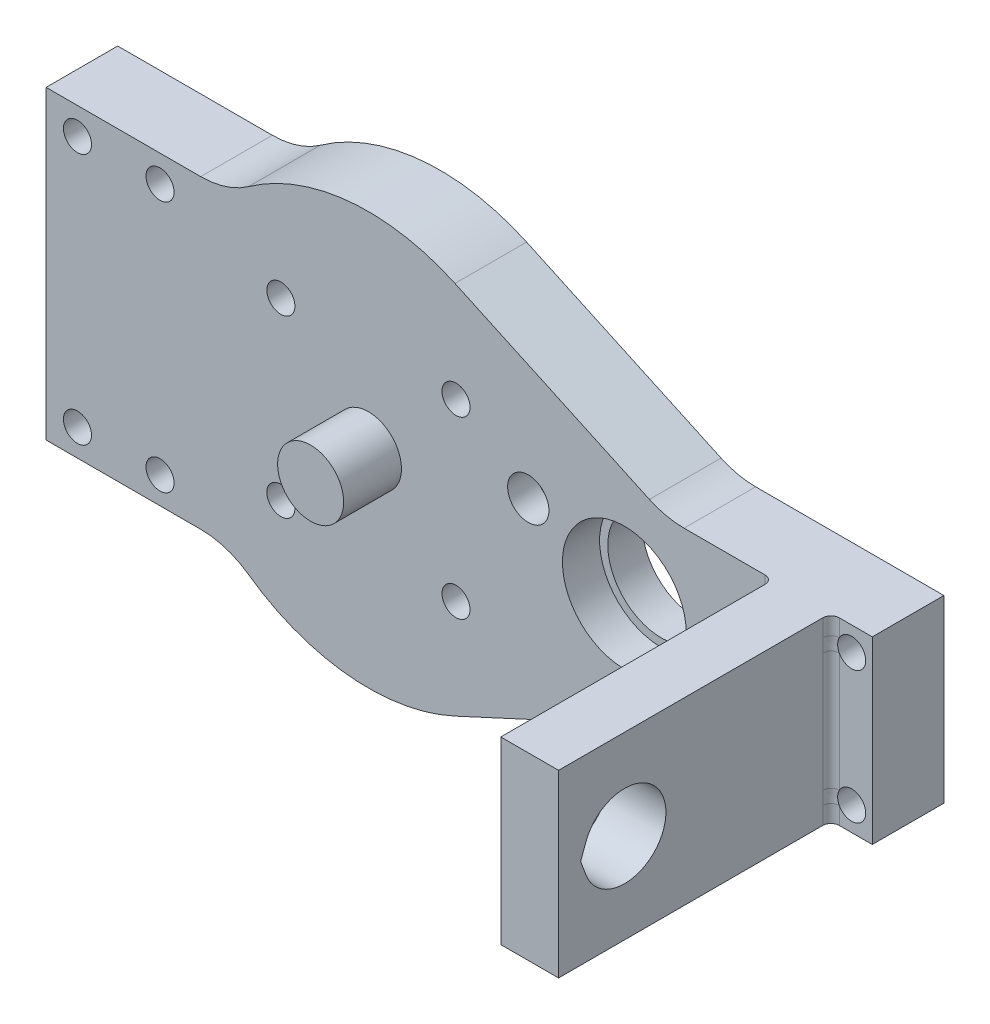
SolidWorks part; units mm, degrees
ref_plane "Front Plane" through (0, 0, 0) normal (0, 0, 1) x (1, 0, 0)
ref_plane "Top Plane" through (0, 0, 0) normal (0, 1, 0) x (1, 0, 0)
ref_plane "Right Plane" through (0, 0, 0) normal (1, 0, 0) x (0, 0, -1)
sketch "Sketch1" plane through (0, 0, 0) normal (0, 0, 1) x (1, 0, 0)
  line L0 (10.4839, 22.6956) -> (36.0323, 10.8939)
  line L1 (36.0323, -10.8939) -> (10.4839, -22.6956)
  circle A0 centre (0, 0) radius 22.215 construction
  circle A1 centre (31, 0) radius 10.2 construction
  arc A2 (10.4839, 22.6956) -> (10.4839, -22.6956) centre (0, 0) ccw
  arc A3 (36.0323, -10.8939) -> (36.0323, 10.8939) centre (31, 0) ccw
  dimension "D1" = 20.4
  dimension "D2" = 44.43
  dimension "D4" = 25
  dimension "D5" = 12
  dimension "D3" = 31
extrude "Boss-Extrude1" add sketch "Sketch1" along normal blind 4.5
sketch "Sketch2" plane through (0, 0, 4.5) normal (0, 0, 1) x (1, 0, 0)
  circle A0 centre (31, 0) radius 7.5
  dimension "D1" = 15
extrude "Cut-Extrude1" cut sketch "Sketch2" against normal through all
sketch "Sketch3" plane through (0, 0, 4.5) normal (0, 0, 1) x (1, 0, 0)
  circle A0 centre (0, 0) radius 4
  dimension "D1" = 8
extrude "Boss-Extrude2" add sketch "Sketch3" along normal blind 7
sketch "Sketch4" plane through (0, 0, 0) normal (0, 0, -1) x (-1, 0, 0)
  line L0 (-36.0323, 10.8939) -> (-56.0323, 10.8939)
  line L1 (-36.0323, -10.8939) -> (-56.0323, -10.8939)
  line L2 (-56.0323, -10.8939) -> (-56.0323, 10.8939)
  line L3 (22.5016, 10.8939) -> (42.5016, 10.8939)
  line L4 (42.5016, 10.8939) -> (42.5016, -10.8939)
  line L5 (42.5016, -10.8939) -> (22.5016, -10.8939)
  arc A0 (-10.4839, -22.6956) -> (-10.4839, 22.6956) centre (0, 0) ccw construction
  arc A1 (22.5016, -10.8939) -> (22.5016, 10.8939) centre (0, 0) ccw
  arc A2 (-36.0323, 10.8939) -> (-36.0323, -10.8939) centre (-31, 0) ccw construction
  arc A3 (-36.0323, 10.8939) -> (-36.0323, -10.8939) centre (-31, 0) ccw
  dimension "D1" = 20
  dimension "D2" = 20
extrude "Boss-Extrude3" add sketch "Sketch4" against normal up to surface (4.5 mm away) up to face at (4, 0, 4.5)
fillet "Fillet1" radius 10 4 edges at (-42.5016, 10.8939, 2.25) (-42.5016, -10.8939, 2.25) (56.0323, -10.8939, 2.25) (56.0323, 10.8939, 2.25)
sketch "Sketch8" plane through (0, 0, 4.5) normal (0, 0, 1) x (1, 0, 0)
  line L0 (56.0323, 0.8939) -> (56.0323, -0.8939) construction
  line L2 (56.0323, 0.8939) -> (56.0323, -0.8939)
  line L3 (55.4014, -4.3896) -> (55.4014, 4.3896)
  line L4 (-42.5016, -0.8939) -> (-42.5016, 0.8939) construction
  line L6 (-42.5016, -0.8939) -> (-42.5016, 0.8939)
  line L7 (-41.8707, 4.3896) -> (-41.8707, -4.3896)
  arc A0 (56.0323, 0.8939) -> (46.0323, 10.8939) centre (46.0323, 0.8939) ccw construction
  arc A1 (46.0323, -10.8939) -> (56.0323, -0.8939) centre (46.0323, -0.8939) ccw construction
  arc A2 (56.0323, 0.8939) -> (55.4014, 4.3896) centre (46.0323, 0.8939) ccw
  arc A3 (55.4014, -4.3896) -> (56.0323, -0.8939) centre (46.0323, -0.8939) ccw
  arc A4 (-32.5016, 10.8939) -> (-42.5016, 0.8939) centre (-32.5016, 0.8939) ccw construction
  arc A5 (-42.5016, -0.8939) -> (-32.5016, -10.8939) centre (-32.5016, -0.8939) ccw construction
  arc A6 (-41.8707, 4.3896) -> (-42.5016, 0.8939) centre (-32.5016, 0.8939) ccw
  arc A7 (-42.5016, -0.8939) -> (-41.8707, -4.3896) centre (-32.5016, -0.8939) ccw
extrude "Cut-Extrude4" cut sketch "Sketch8" against normal through all
sketch "Sketch9" plane through (0, 0, 4.5) normal (0, 0, 1) x (1, 0, 0)
  circle A0 centre (0, 0) radius 15 construction
  circle A1 centre (-10.6066, 10.6066) radius 1
  circle A2 centre (10.6066, 10.6066) radius 1
  circle A3 centre (10.6066, -10.6066) radius 1
  circle A4 centre (-10.6066, -10.6066) radius 1
  point P14 (0, 0)
  dimension "D1" = 30
  dimension "D2" = 2
  dimension "D3" = 4
extrude "Cut-Extrude5" cut sketch "Sketch9" against normal through all
sketch "Sketch10" plane through (0, 0, 4.5) normal (0, 0, 1) x (1, 0, 0)
  circle A0 centre (-10.6066, 10.6066) radius 1.7
  circle A1 centre (10.6066, 10.6066) radius 1.7
  circle A2 centre (10.6066, -10.6066) radius 1.7
  circle A3 centre (-10.6066, -10.6066) radius 1.7
  dimension "D1" = 3.4
extrude "Cut-Extrude6" cut sketch "Sketch10" against normal blind 2.4
sketch "Sketch11" plane through (0, 0, 0) normal (0, 0, -1) x (-1, 0, 0)
  line L0 (-40.9602, 14.6461) -> (-73.6718, 18.9155)
  line L1 (-73.6718, 18.9155) -> (-68.6403, -15.6759)
  line L2 (-68.6403, -15.6759) -> (-41.445, -13.2122)
  arc A0 (-40.9602, 14.6461) -> (-41.445, -13.2122) centre (0, 0) ccw
  dimension "D1" = 87
extrude "Cut-Extrude7" cut sketch "Sketch11" against normal up to surface (4.5 mm away) up to face at (-8.9066, -10.6066, 4.5)
fillet "Fillet2" radius 10 2 edges at (42.1138, -10.8939, 2.25) (42.1138, 10.8939, 2.25)
sketch "Sketch12" plane through (0, 0, 4.5) normal (0, 0, 1) x (1, 0, 0)
  line L0 (-22.5016, 10.8939) -> (-42.5927, 14.8195)
  line L1 (-42.5927, 14.8195) -> (-48.1481, -13.6126)
  line L2 (-48.1481, -13.6126) -> (-27.4273, -14.3153)
  line L3 (-27.4273, -14.3153) -> (-22.5016, -10.8939)
  arc A0 (-22.5016, 10.8939) -> (-22.5016, -10.8939) centre (0, 0) ccw
extrude "Cut-Extrude8" cut sketch "Sketch12" against normal through all
sketch "Sketch23" plane through (0, 0, 0) normal (0, 0, -1) x (-1, 0, 0)
  line L2 (-36.0323, -10.8939) -> (-10.4839, -22.6956)
  line L3 (-10.4839, 22.6956) -> (-36.0323, 10.8939)
  line L4 (-36.0323, -10.8939) -> (-10.4839, -22.6956)
  line L5 (-10.4839, 22.6956) -> (-36.0323, 10.8939)
  circle A0 centre (-10.6066, -10.6066) radius 1 construction
  circle A1 centre (10.6066, -10.6066) radius 1 construction
  circle A2 centre (10.6066, 10.6066) radius 1 construction
  circle A3 centre (-10.6066, 10.6066) radius 1 construction
  arc A4 (-10.4839, -22.6956) -> (-10.4839, 22.6956) centre (0, 0) ccw
  arc A5 (-36.0323, 10.8939) -> (-43.4709, 1.5916) centre (-33.4776, 1.2257) ccw
  arc A6 (-43.4709, 1.5916) -> (-43.4709, -1.5916) centre (0, 0) ccw
  arc A7 (-43.4709, -1.5916) -> (-36.0323, -10.8939) centre (-33.4776, -1.2257) ccw
  arc A8 (-10.4839, -22.6956) -> (-10.4839, 22.6956) centre (0, 0) ccw
  arc A9 (-36.0323, 10.8939) -> (-43.4709, 1.5916) centre (-33.4776, 1.2257) ccw
  arc A10 (-43.4709, 1.5916) -> (-43.4709, -1.5916) centre (0, 0) ccw
  arc A11 (-43.4709, -1.5916) -> (-36.0323, -10.8939) centre (-33.4776, -1.2257) ccw
  circle A12 centre (-10.6066, -10.6066) radius 1
  circle A13 centre (10.6066, -10.6066) radius 1
  circle A14 centre (10.6066, 10.6066) radius 1
  circle A15 centre (-10.6066, 10.6066) radius 1
  circle A16 centre (-31, 0) radius 6.5
  dimension "D2" = 13
  dimension "D1" = 0
extrude "Boss-Extrude6" add sketch "Sketch23" along normal blind 4.175
sketch "Sketch24" plane through (0, 0, -4.175) normal (0, 0, -1) x (-1, 0, 0)
  line L0 (-10.6066, 10.6066) -> (10.6066, 10.6066) construction
ref_axis "Axis1" through (10.6066, 10.6066, -4.175) along (-1, 0, 0)
sketch "Sketch25" plane through (0, 0, -4.175) normal (0, 0, -1) x (-1, 0, 0)
  line L1 (-36.0323, 10.8939) -> (-56.0323, 10.8939)
  line L3 (-36.0323, -10.8939) -> (-56.0323, -10.8939)
  line L4 (-56.0323, 10.8939) -> (-56.0323, -10.8939)
  arc A0 (-43.4709, -1.5916) -> (-36.0323, -10.8939) centre (-33.4776, -1.2257) ccw construction
  arc A1 (-43.4709, 1.5916) -> (-43.4709, -1.5916) centre (0, 0) ccw construction
  arc A2 (-36.0323, 10.8939) -> (-43.4709, 1.5916) centre (-33.4776, 1.2257) ccw construction
  arc A3 (-43.4709, -1.5916) -> (-36.0323, -10.8939) centre (-33.4776, -1.2257) ccw
  arc A4 (-43.4709, 1.5916) -> (-43.4709, -1.5916) centre (0, 0) ccw
  arc A5 (-36.0323, 10.8939) -> (-43.4709, 1.5916) centre (-33.4776, 1.2257) ccw
  dimension "D1" = 20
extrude "Boss-Extrude7" add sketch "Sketch25" against normal up to surface (8.675 mm away) up to face at (24.5985, 0, 4.5)
sketch "Sketch26" plane through (0, 0, 4.5) normal (0, 0, 1) x (1, 0, 0)
  line L0 (36.0323, 10.8939) -> (56.0323, 10.8939) construction
  line L1 (56.0323, -10.8939) -> (47.0323, -10.8939)
  line L2 (56.0323, -10.8939) -> (56.0323, 10.8939)
  line L3 (56.0323, 10.8939) -> (47.0323, 10.8939)
  line L4 (47.0323, -10.8939) -> (47.0323, 10.8939)
  dimension "D1" = 9
extrude "Boss-Extrude8" add sketch "Sketch26" along normal blind 33
sketch "Sketch27" plane through (56.0323, 0, 0) normal (1, 0, 0) x (0, 0, -1)
  circle A0 centre (-29.5, 0) radius 5
extrude "Cut-Extrude9" cut sketch "Sketch27" against normal up to next
sketch "Sketch28" plane through (0, 0, -4.175) normal (0, 0, -1) x (-1, 0, 0)
  line L1 (16.8152, 18.5) -> (50.7321, 18.5)
  line L3 (16.8152, -18.5) -> (50.7321, -18.5)
  line L4 (0, 0) -> (54, 0) construction
  line L5 (54, 0) -> (25.875, 18.5) construction
  line L6 (54, 0) -> (31.6196, -18.5) construction
  line L7 (50.7321, -18.5) -> (25, 0) construction
  line L8 (25, 0) -> (50.7321, 18.5) construction
  line L9 (50.7321, 18.5) -> (50.7321, -18.5)
  arc A0 (50.7321, -18.5) -> (50.7321, 18.5) centre (0, 0) ccw construction
  arc A2 (-10.4839, -22.6956) -> (-10.4839, 22.6956) centre (0, 0) ccw construction
  arc A3 (16.8152, -18.5) -> (16.8152, 18.5) centre (0, 0) ccw
  dimension "D1" = 108
  dimension "D3" = 37
extrude "Boss-Extrude9" add sketch "Sketch28" against normal up to surface (8.675 mm away) up to face at (38.5, 0, 4.5)
sketch "Sketch29" plane through (0, 0, 4.5) normal (0, 0, 1) x (1, 0, 0)
  line L0 (-50.7321, 18.5) -> (-33.7737, 18.5)
  line L1 (-50.7321, 18.5) -> (-50.7321, -18.5)
  line L2 (-50.7321, -18.5) -> (-33.7737, -18.5)
  line L3 (-16.8152, -18.5) -> (-50.7321, -18.5) construction
  line L4 (-50.7321, 18.5) -> (-16.8152, 18.5) construction
  line L5 (-48.7321, 16.5) -> (-48.7321, -16.5)
  line L6 (-48.7321, 16.5) -> (-50.7321, 18.5) construction
  line L7 (-48.7321, -16.5) -> (-50.7321, -18.5) construction
  line L8 (-48.7321, 16.5) -> (-33.7737, 16.5)
  line L9 (-33.7737, 16.5) -> (-33.7737, 18.5)
  line L10 (-33.7737, -18.5) -> (-33.7737, -16.5)
  line L11 (-33.7737, -16.5) -> (-48.7321, -16.5)
  dimension "D1" = 33
  dimension "D2" = 2
extrude "Boss-Extrude10" add sketch "Sketch29" along normal blind 105
fillet "Fillet4" radius 10 4 edges at (36.0323, 10.8939, 0.1625) (36.0323, -10.8939, 0.1625) (-16.8152, 18.5, 0.1625) (-16.8152, -18.5, 0.1625)
sketch "Sketch30" plane through (56.0323, 0, 0) normal (1, 0, 0) x (0, 0, -1)
  line L0 (-34.1928, 1.7255) -> (-34.8273, 0)
  line L1 (-34.8273, 0) -> (-34.1928, -1.7255)
  line L2 (-34.5, 0) -> (-34.8273, 0) construction
  circle A0 centre (-29.5, 0) radius 5 construction
  arc A1 (-34.1928, 1.7255) -> (-34.1928, -1.7255) centre (-29.5, 0) ccw
extrude "Cut-Extrude10" cut sketch "Sketch30" against normal up to surface (9 mm away) up to face at (47.0323, 0, 24.5)
sketch "Sketch31" plane through (0, 0, 4.5) normal (0, 0, 1) x (1, 0, 0)
  line L0 (-46.6706, 12.5) -> (-48.7321, 16.5) construction
  line L1 (-46.6706, 12.5) -> (-34.6706, 12.5)
  line L2 (-46.6706, 12.5) -> (-46.6706, -12.5)
  line L3 (-46.6706, -12.5) -> (-34.6706, -12.5)
  line L4 (-34.6706, 12.5) -> (-34.6706, -12.5)
  line L5 (-46.6706, -12.5) -> (-48.7321, -16.5) construction
  dimension "D1" = 25
  dimension "D2" = 12
  dimension "D3" = 4.5
extrude "Cut-Extrude11" cut sketch "Sketch31" against normal through all
sketch "Sketch32" plane through (0, 0, 4.5) normal (0, 0, 1) x (1, 0, 0)
  line L0 (-33.7737, 18.5) -> (-33.7737, 16.5)
  line L1 (-33.7737, 16.5) -> (-27.7321, 16.5)
  line L2 (-27.7321, 16.5) -> (-27.7321, -16.5)
  line L3 (-27.7321, -16.5) -> (-33.7737, -16.5)
  line L4 (-33.7737, -16.5) -> (-33.7737, -18.5)
  line L5 (-33.7737, -18.5) -> (-27.045, -18.5)
  line L6 (-20.3162, -18.5) -> (-33.7737, -18.5) construction
  line L7 (-27.045, -18.5) -> (-27.045, 18.5)
  line L8 (-33.7737, 18.5) -> (-20.3162, 18.5) construction
  line L9 (-27.045, 18.5) -> (-33.7737, 18.5)
extrude "Boss-Extrude11" add sketch "Sketch32" along normal blind 10
sketch "Sketch33" plane through (-27.045, 0, 0) normal (1, 0, 0) x (0, 0, -1)
  line L0 (-4.5, -22.6956) -> (-4.5, -11.8156) construction
  line L1 (-14.5, 16.5) -> (-4.5, 16.5)
  line L2 (-14.5, 16.5) -> (-14.5, -16.5)
  line L3 (-14.5, -16.5) -> (-4.5, -16.5)
  line L4 (-4.5, 16.5) -> (-4.5, -16.5)
  line L5 (-109.5, -16.5) -> (-4.5, -16.5) construction
extrude "Cut-Extrude12" cut sketch "Sketch33" against normal up to next
sketch "Sketch34" plane through (-48.7321, 0, 0) normal (1, 0, 0) x (0, 0, -1)
  line L0 (-109.5, 16.5) -> (-109.5, 18.5) construction
  line L1 (-109.5, 17.5) -> (-4.5, 17.5)
  line L2 (-109.5, 17.5) -> (-109.5, -17.5)
  line L3 (-109.5, -17.5) -> (-4.5, -17.5)
  line L4 (-4.5, 17.5) -> (-4.5, -17.5)
  line L5 (-4.5, -18.5) -> (-4.5, -16.5) construction
extrude "Cut-Extrude13" cut sketch "Sketch34" along normal up to surface (21.6872 mm away) up to face at (-27.045, -17.5, 9.5)
sketch "Sketch35" plane through (56.0323, 0, 0) normal (1, 0, 0) x (0, 0, -1)
  circle A0 centre (-29.5, 0) radius 5.5
  dimension "D1" = 11
extrude "Cut-Extrude14" [suppressed] cut sketch "Sketch35" against normal up to next
sketch "Sketch36" [suppressed] plane through (56.0323, 0, 0) normal (1, 0, 0) x (0, 0, -1)
  line L0 (-34.3284, 2.6337) -> (-35.765, 0)
  line L1 (-35.765, 0) -> (-34.3284, -2.6337)
  line L2 (-35.765, 0) -> (0, 0) construction
  circle A0 centre (-29.5, 0) radius 5.5 construction
  arc A1 (-34.3284, -2.6337) -> (-34.3284, 2.6337) centre (-29.5, 0) cw
  dimension "D1" = 3
extrude "Cut-Extrude15" [suppressed] cut sketch "Sketch36" against normal up to next
sketch "Sketch37" plane through (0, 0, 37.5) normal (0, 0, 1) x (1, 0, 0)
  line L0 (47.0323, -10.8939) -> (56.0323, -10.8939) construction
  line L1 (47.0323, 10.8939) -> (49.0323, 10.8939)
  line L2 (47.0323, 10.8939) -> (47.0323, -10.8939)
  line L3 (47.0323, -10.8939) -> (49.0323, -10.8939)
  line L4 (49.0323, 10.8939) -> (49.0323, -10.8939)
  dimension "D1" = 2
extrude "Cut-Extrude16" cut sketch "Sketch37" against normal up to surface (33 mm away) up to face at (-0.8985, 0, 4.5)
sketch "Sketch38" plane through (0, 0, 4.5) normal (0, 0, 1) x (1, 0, 0)
  line L0 (19.3604, 4.5575) -> (42.6396, -4.5575) construction
  circle A0 centre (31, 0) radius 12.5 construction
  circle A1 centre (19.3604, 4.5575) radius 1.5
  circle A2 centre (42.6396, -4.5575) radius 1.5
  dimension "D1" = 25
  dimension "D2" = 3
extrude "Cut-Extrude17" cut sketch "Sketch38" against normal blind 10
sketch "Sketch39" plane through (0, 0, 4.5) normal (0, 0, 1) x (1, 0, 0)
  circle A0 centre (19.3604, 4.5575) radius 2.5
  circle A1 centre (42.6396, -4.5575) radius 2.5
  dimension "D1" = 5
extrude "Cut-Extrude18" cut sketch "Sketch39" against normal blind 3.5
sketch "Sketch40" plane through (0, 0, 4.5) normal (0, 0, 1) x (1, 0, 0)
  line L1 (-50.7321, 18.5) -> (-27.045, 18.5)
  line L2 (-50.7321, 18.5) -> (-50.7321, -18.5)
  line L3 (-50.7321, -18.5) -> (-27.045, -18.5)
  line L4 (-27.045, 18.5) -> (-27.045, -18.5)
extrude "Cut-Extrude19" cut sketch "Sketch40" along normal blind 133.5
sketch "Sketch41" plane through (0, 0, 4.5) normal (0, 0, 1) x (1, 0, 0)
  line L1 (-46.6706, 12.5) -> (-34.6706, 12.5)
  line L2 (-46.6706, 12.5) -> (-46.6706, -12.5)
  line L3 (-46.6706, -12.5) -> (-34.6706, -12.5)
  line L4 (-34.6706, 12.5) -> (-34.6706, -12.5)
extrude "Boss-Extrude12" add sketch "Sketch41" against normal up to surface (8.675 mm away) up to face at (17.8604, 4.5575, -4.175)
sketch "Sketch42" plane through (0, 0, 4.5) normal (0, 0, 1) x (1, 0, 0)
  line L0 (-20.3162, -18.5) -> (-50.7321, -18.5) construction
  line L1 (-50.7321, 18.5) -> (-39.0453, 18.5)
  line L2 (-50.7321, 18.5) -> (-50.7321, -18.5)
  line L3 (-50.7321, -18.5) -> (-39.0453, -18.5)
  line L4 (-39.0453, 18.5) -> (-39.0453, -18.5)
extrude "Cut-Extrude20" cut sketch "Sketch42" against normal through all
sketch "Sketch43" plane through (0, 0, 4.5) normal (0, 0, 1) x (1, 0, 0)
  line L0 (-39.0453, 18.5) -> (-35.2453, 15.2504) construction
  line L1 (-35.2453, 15.2504) -> (-25.2453, 15.2504) construction
  line L2 (-35.2453, 15.2504) -> (-35.2453, -15.2504) construction
  line L3 (-35.2453, -15.2504) -> (-25.2453, -15.2504) construction
  line L4 (-25.2453, 15.2504) -> (-25.2453, -15.2504) construction
  line L5 (-35.2453, -15.2504) -> (-39.0453, -18.5) construction
  line L7 (-39.0453, -18.5) -> (-39.0453, 18.5) construction
  circle A0 centre (-35.2453, 15.2504) radius 1
  circle A1 centre (-35.2453, -15.2504) radius 1
  circle A2 centre (-25.2453, 15.2504) radius 1
  circle A3 centre (-25.2453, -15.2504) radius 1
  dimension "D1" = 2
  dimension "D2" = 5
  dimension "D3" = 10
  dimension "D4" = 3.8
extrude "Cut-Extrude21" cut sketch "Sketch43" against normal through all
sketch "Sketch44" plane through (0, 0, 4.5) normal (0, 0, 1) x (1, 0, 0)
  circle A0 centre (-35.2453, 15.2504) radius 1.7
  circle A1 centre (-25.2453, 15.2504) radius 1.7
  circle A2 centre (-35.2453, -15.2504) radius 1.7
  circle A3 centre (-25.2453, -15.2504) radius 1.7
  circle A4 centre (-10.6066, 10.6066) radius 1.7 construction
extrude "Cut-Extrude22" cut sketch "Sketch44" against normal blind 3
sketch "Sketch45" plane through (0, 0, -4.175) normal (0, 0, -1) x (-1, 0, 0)
  line L0 (-56.0323, -10.8939) -> (-38.2303, -10.8939) construction
  line L1 (-56.0323, 10.8939) -> (-61.0323, 10.8939)
  line L2 (-56.0323, 10.8939) -> (-56.0323, -10.8939)
  line L3 (-56.0323, -10.8939) -> (-61.0323, -10.8939)
  line L4 (-61.0323, 10.8939) -> (-61.0323, -10.8939)
  line L5 (-61.0323, 10.8939) -> (-58.5323, 8) construction
  line L6 (-58.5323, 8) -> (-58.5323, -8) construction
  line L7 (-58.5323, -8) -> (-61.0323, -10.8939) construction
  line L8 (-58.5323, -8) -> (-56.0323, -10.8939) construction
  circle A0 centre (-58.5323, 8) radius 1
  circle A1 centre (-58.5323, -8) radius 1
  dimension "D3" = 2
  dimension "D1" = 5
  dimension "D2" = 16
extrude "Boss-Extrude13" add sketch "Sketch45" against normal up to surface (8.675 mm away) up to face at (-23.5453, 15.2504, 4.5)
sketch "Sketch46" plane through (0, 0, 4.5) normal (0, 0, 1) x (1, 0, 0)
  circle A0 centre (58.5323, 8) radius 1.7
  circle A1 centre (58.5323, -8) radius 1.7
  circle A2 centre (10.6066, -10.6066) radius 1.7 construction
extrude "Cut-Extrude23" cut sketch "Sketch46" against normal blind 3
fillet "Fillet5" radius 1 2 edges at (56.0323, 0, 4.5) (49.0323, 0, 4.5)
